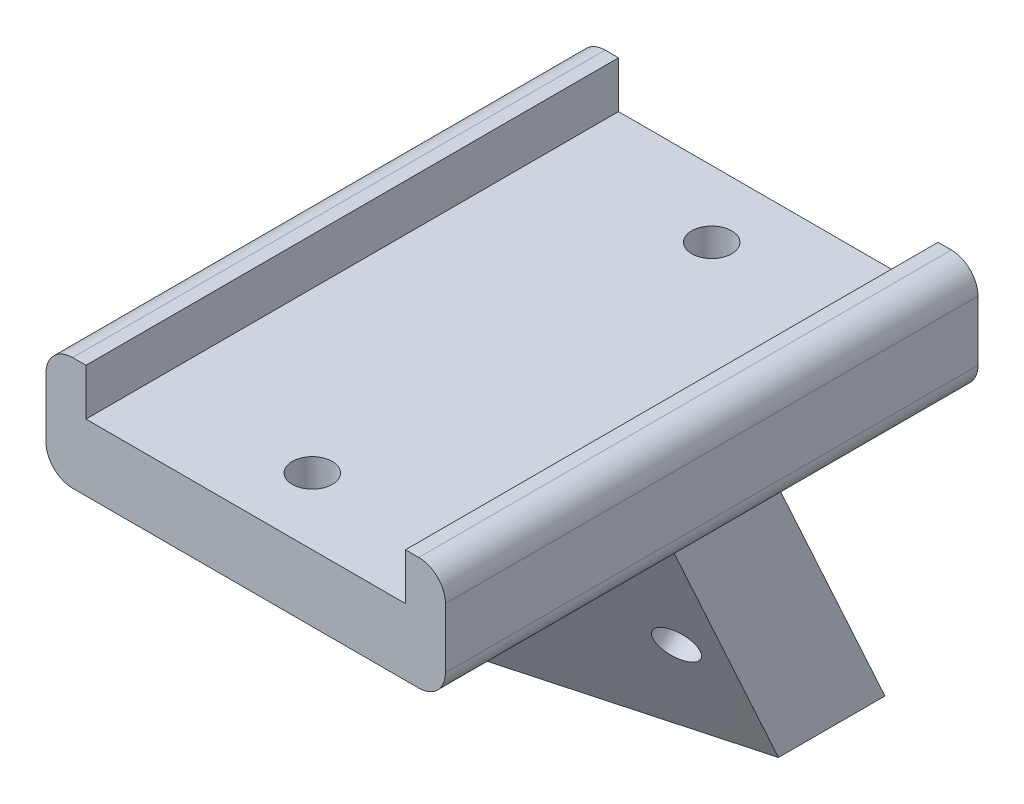
SolidWorks part; units mm, degrees
ref_plane "Front Plane" through (0, 0, 0) normal (0, 0, 1) x (1, 0, 0)
ref_plane "Top Plane" through (0, 0, 0) normal (0, 1, 0) x (1, 0, 0)
ref_plane "Right Plane" through (0, 0, 0) normal (1, 0, 0) x (0, 0, -1)
sketch "Sketch1" plane through (0, 0, 0) normal (0, 1, 0) x (1, 0, 0)
  line L1 (-11, -20) -> (11, -20)
  line L2 (-11, -20) -> (-11, 20)
  line L3 (-11, 20) -> (11, 20)
  line L4 (11, -20) -> (11, 20)
  line L5 (-11, -20) -> (11, 20) construction
  line L6 (-11, 20) -> (11, -20) construction
  circle A0 centre (0, 15) radius 1.5
  circle A1 centre (0, -15) radius 1.5
  point P0 (0, 0)
  dimension "D1" = 30
  dimension "D2" = 15
  dimension "D3" = 3
  dimension "D4" = 3
  dimension "D5" = 40
  dimension "D6" = 22
extrude "Boss-Extrude1" add sketch "Sketch1" along normal blind 5
sketch "Sketch2" plane through (0, 0, 0) normal (0, -1, 0) x (1, 0, 0)
  line L0 (-11, 6) -> (11, 0.1051)
  line L1 (-11, -20) -> (-11, 20) construction
  line L2 (11, 20) -> (11, -20) construction
  line L3 (11, 0.1051) -> (11, -7.8949)
  line L4 (11, -7.8949) -> (-11, -2)
  line L5 (-11, -2) -> (-11, 6)
  dimension "D1" = 8
  dimension "D2" = 8
  dimension "D3" = 105
  dimension "D4" = 14
sketch "Sketch4" plane through (0, 0, -20) normal (0, 0, -1) x (-1, 0, 0)
  line L0 (-11, 5) -> (-12, 5)
  line L1 (-12, 5) -> (-12, 8.5)
  line L2 (-12, 8.5) -> (-15, 8.5)
  line L3 (-15, 8.5) -> (-15, 0)
  line L4 (-15, 0) -> (-11, 0)
  line L5 (-11, 0) -> (-11, 5)
  line L6 (0, 0) -> (0, 5) construction
  line L7 (-11, 0) -> (11, 0) construction
  line L8 (-11, 5) -> (11, 5) construction
  line L9 (11, 0) -> (11, 5)
  line L10 (15, 0) -> (11, 0)
  line L11 (15, 8.5) -> (15, 0)
  line L12 (12, 8.5) -> (15, 8.5)
  line L13 (12, 5) -> (12, 8.5)
  line L14 (11, 5) -> (12, 5)
  dimension "D1" = 1
  dimension "D2" = 3
  dimension "D3" = 3.5
extrude "Boss-Extrude3" add sketch "Sketch4" against normal up to surface (40 mm away) up to face at (0, 2.5, 20)
fillet "Fillet1" radius 2 4 edges at (15, 0, 0) (15, 8.5, 0) (-15, 0, 0) (-15, 8.5, 0)
ref_plane "Plane1" through (0, -20, 0) normal (0, 1, 0) x (1, 0, 0)
sketch "Sketch6" plane through (0, -20, 0) normal (0, 1, 0) x (1, 0, 0)
  line L0 (11.018, 16.9927) -> (-11, 11)
  line L1 (-11, 11) -> (-11, 3)
  line L2 (-11, 3) -> (11.018, 8.9927)
  line L3 (11.018, 8.9927) -> (11.018, 16.9927)
  line L4 (-13, -20) -> (-13, 20) construction
  line L5 (-13, -20) -> (13, -20) construction
  dimension "D1" = 2
  dimension "D2" = 8
  dimension "D3" = 8
  dimension "D4" = 23
loft "Loft1" add profiles "Sketch6", "Sketch2" connector at (11.018, -20, -8.9927) connector at (11, 0, 0.1051)
ref_plane "Plane3" through (-1.0415, 1.7397, -3.8266) normal (-0.2405, 0.4017, -0.8836) x (-0.9707, -0.0995, 0.2189)
sketch "Sketch9" plane through (-1.0415, 1.7397, -3.8266) normal (-0.2405, 0.4017, -0.8836) x (-0.9707, -0.0995, 0.2189)
  line L1 (-12.4241, -25.2396) -> (-12.4056, -3.2675) construction
  line L2 (10.2393, -0.8278) -> (-12.4056, -3.2675) construction
  line L3 (10.2596, -22.7593) -> (10.2393, -0.8278) construction
  circle A0 centre (-7.4136, -12.7876) radius 1.5
  circle A1 centre (5.2491, -11.4233) radius 1.5
  dimension "D1" = 5
  dimension "D2" = 10
  dimension "D3" = 5
  dimension "D4" = 10
  dimension "D5" = 3
  dimension "D6" = 3
extrude "Cut-Extrude1" cut sketch "Sketch9" against normal up to surface and the other way up to surface up to face at (0.0045, -15, -3.7219) other way up to face at (0.009, -15, -11.7464)
